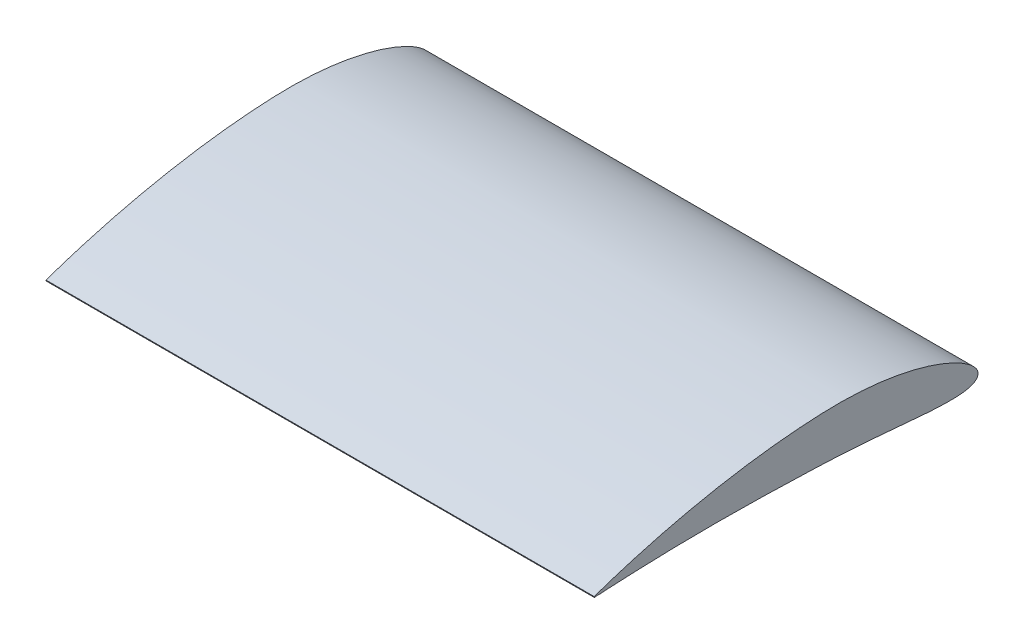
SolidWorks part; units mm, degrees
material "Thornel Mat VMA Foam Core"
ref_plane "Front Plane" through (0, 0, 0) normal (0, 0, 1) x (1, 0, 0)
ref_plane "Top Plane" through (0, 0, 0) normal (0, 1, 0) x (1, 0, 0)
ref_plane "Right Plane" through (0, 0, 0) normal (1, 0, 0) x (0, 0, -1)
curve "Curve1"
  spline degree 3 poles (0, 0.0012, 1.0003) (0, 0.0015, 0.9994) (0, 0.0028, 0.9958) (0, 0.0055, 0.9879) (0, 0.0099, 0.9747) (0, 0.0159, 0.9565) (0, 0.0233, 0.9333) (0, 0.0318, 0.9054) (0, 0.0411, 0.8731) (0, 0.051, 0.8366) (0, 0.0612, 0.7964) (0, 0.0713, 0.7528) (0, 0.0811, 0.7063) (0, 0.0903, 0.6574) (0, 0.0985, 0.6067) (0, 0.1057, 0.5546) (0, 0.1115, 0.5018) (0, 0.1158, 0.4488) (0, 0.1186, 0.3959) (0, 0.1189, 0.3436) (0, 0.1164, 0.2927) (0, 0.1112, 0.2442) (0, 0.1037, 0.1988) (0, 0.0942, 0.157) (0, 0.0831, 0.1194) (0, 0.0711, 0.0865) (0, 0.0584, 0.0585) (0, 0.0457, 0.0357) (0, 0.0334, 0.0184) (0, 0.0218, 0.0064) (0, 0.0108, -0.0005) (0, -0.0003, -0.0011) (0, -0.0092, 0.0055) (0, -0.0148, 0.017) (0, -0.0185, 0.0329) (0, -0.0204, 0.0533) (0, -0.0208, 0.0781) (0, -0.0198, 0.107) (0, -0.0176, 0.1398) (0, -0.0147, 0.176) (0, -0.0111, 0.2153) (0, -0.0074, 0.2574) (0, -0.0037, 0.3019) (0, -0.0005, 0.3484) (0, 0.002, 0.397) (0, 0.0037, 0.4471) (0, 0.0055, 0.4983) (0, 0.0069, 0.5496) (0, 0.0079, 0.6006) (0, 0.0085, 0.6505) (0, 0.0086, 0.699) (0, 0.0083, 0.7455) (0, 0.0076, 0.7894) (0, 0.0065, 0.8302) (0, 0.0053, 0.8675) (0, 0.0039, 0.9007) (0, 0.0027, 0.9296) (0, 0.0013, 0.9539) (0, 0.0006, 0.9727) (0, -0.0011, 0.9872) (0, 0, 0.9944) (0, -0.002, 0.9999) (0, -0.0005, 1) (0, 0, 1) knots 0 0 0 0 0.001372 0.005465 0.012235 0.021602 0.033461 0.047671 0.064081 0.082496 0.102719 0.124527 0.147676 0.171913 0.196978 0.222597 0.248497 0.274385 0.300041 0.32569 0.350525 0.37428 0.396711 0.417577 0.436654 0.453744 0.46868 0.481329 0.491631 0.499616 0.505546 0.510185 0.514824 0.520702 0.528516 0.538466 0.550543 0.564643 0.580638 0.598345 0.617584 0.638174 0.659922 0.682632 0.706121 0.730727 0.7557 0.780732 0.805564 0.829932 0.85357 0.876213 0.89761 0.917519 0.935698 0.951943 0.966047 0.97784 0.987174 0.993932 0.998018 0.999386 1 1 1 1
sketch "Sketch1" plane through (0, 0, 0) normal (1, 0, 0) x (0, 0, -1)
  line L0 (-354.7873, -0.0303) -> (-354.8762, 0.4104)
  line L1 (-354.7873, -0.0303) -> (0.8093, 1.5275) construction
  line L2 (0.8093, 1.5275) -> (0.7921, 5.4415) construction
  spline S1 degree 3 poles (-354.8762, 0.4104) (-354.5599, 0.5194) (-353.2997, 0.9536) (-350.4787, 1.9271) (-345.801, 3.4978) (-336.0241, 6.7216) (-319.6545, 11.7989) (-300.5983, 17.1306) (-282.4229, 21.7243) (-261.1758, 26.6516) (-238.6223, 31.1455) (-208.7748, 36.0048) (-183.9617, 39.0905) (-158.9023, 41.1132) (-140.0967, 42.1114) (-121.5167, 42.2289) (-103.4222, 41.3211) (-86.1884, 39.4787) (-70.0435, 36.8105) (-55.1998, 33.4329) (-41.8434, 29.5109) (-30.1305, 25.2201) (-20.187, 20.7343) (-12.1072, 16.2263) (-5.9269, 11.8553) (-1.6792, 7.7165) (0.7658, 3.7968) (0.9875, -0.1483) (-1.3511, -3.3089) (-5.4508, -5.2881) (-11.0873, -6.5875) (-18.3491, -7.2685) (-27.1638, -7.4049) (-37.4471, -7.0538) (-49.0831, -6.3019) (-61.9524, -5.238) (-75.9299, -3.9839) (-96.4067, -2.1536) (-117.9372, -0.4584) (-140.4848, 0.6745) (-158.2965, 1.2867) (-176.4839, 1.9179) (-200.672, 2.5862) (-224.5411, 2.9791) (-247.8302, 3.0285) (-264.3373, 2.9074) (-279.9331, 2.6564) (-294.438, 2.2829) (-307.6819, 1.8521) (-319.5134, 1.3711) (-329.7674, 0.9129) (-338.3889, 0.4268) (-345.077, 0.1915) (-350.2276, -0.4064) (-352.7802, -0.0354) (-354.7446, -0.7581) (-354.7772, -0.2025) (-354.7873, -0.0303) knots 0 0 0 0 0.001372 0.005465 0.012235 0.021602 0.047671 0.082496 0.102719 0.124527 0.171913 0.196978 0.248497 0.274385 0.300041 0.32569 0.350525 0.37428 0.396711 0.417577 0.436654 0.453744 0.46868 0.481329 0.491631 0.499616 0.505546 0.510185 0.514824 0.520702 0.528516 0.538466 0.550543 0.564643 0.580638 0.598345 0.617584 0.638174 0.682632 0.706121 0.730727 0.7557 0.780732 0.829932 0.85357 0.876213 0.89761 0.917519 0.935698 0.951943 0.966047 0.97784 0.987174 0.993932 0.998018 0.999386 1 1 1 1
  dimension "D1" = 355.6
extrude "Boss-Extrude1" add sketch "Sketch1" along normal blind 254 and the other way blind 254
